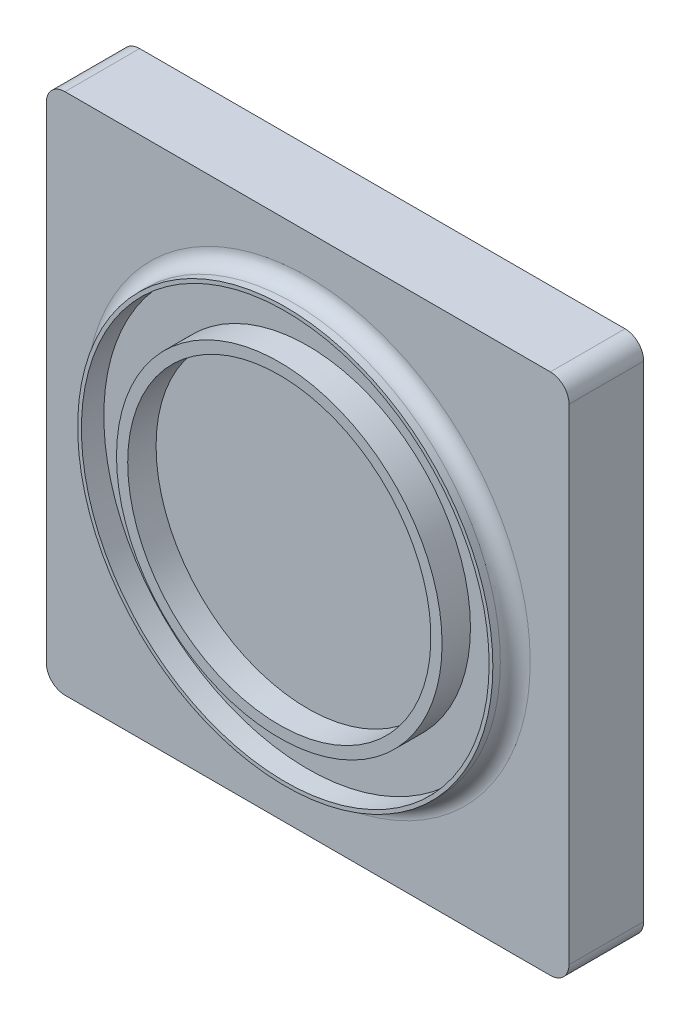
SolidWorks part; units mm, degrees
ref_plane "Front Plane" through (0, 0, 0) normal (0, 0, 1) x (1, 0, 0)
ref_plane "Top Plane" through (0, 0, 0) normal (0, 1, 0) x (1, 0, 0)
ref_plane "Right Plane" through (0, 0, 0) normal (1, 0, 0) x (0, 0, -1)
sketch "Sketch1" plane through (0, 0, 0) normal (0, 0, 1) x (1, 0, 0)
  line L1 (-35, 35) -> (35, 35)
  line L2 (-35, 35) -> (-35, -35)
  line L3 (-35, -35) -> (35, -35)
  line L4 (35, 35) -> (35, -35)
  line L5 (-35, 35) -> (35, -35) construction
  line L6 (-35, -35) -> (35, 35) construction
  point P0 (0, 0)
  dimension "D1" = 70
  dimension "D2" = 70
extrude "Boss-Extrude1" add sketch "Sketch1" along normal blind 10
fillet "Fillet1" radius 2.5 4 edges at (35, 35, 5) (-35, 35, 5) (35, -35, 5) (-35, -35, 5)
sketch "Sketch5" plane through (0, 0, 10) normal (0, 0, 1) x (1, 0, 0)
  circle A0 centre (0, 0) radius 27.8
  circle A1 centre (0, 0) radius 27.3
  dimension "D1" = 54.6
  dimension "D2" = 55.6
extrude "Boss-Extrude5" add sketch "Sketch5" along normal blind 3
fillet "Fillet2" radius 2 1 edges at (27.8, 0, 10)
sketch "Sketch10" plane through (0, 0, 10) normal (0, 0, 1) x (1, 0, 0)
  circle A0 centre (0, 0) radius 21.8
  circle A1 centre (0, 0) radius 20.3
  dimension "D1" = 43.6
  dimension "D2" = 40.6
extrude "Boss-Extrude7" add sketch "Sketch10" along normal blind 3.8
